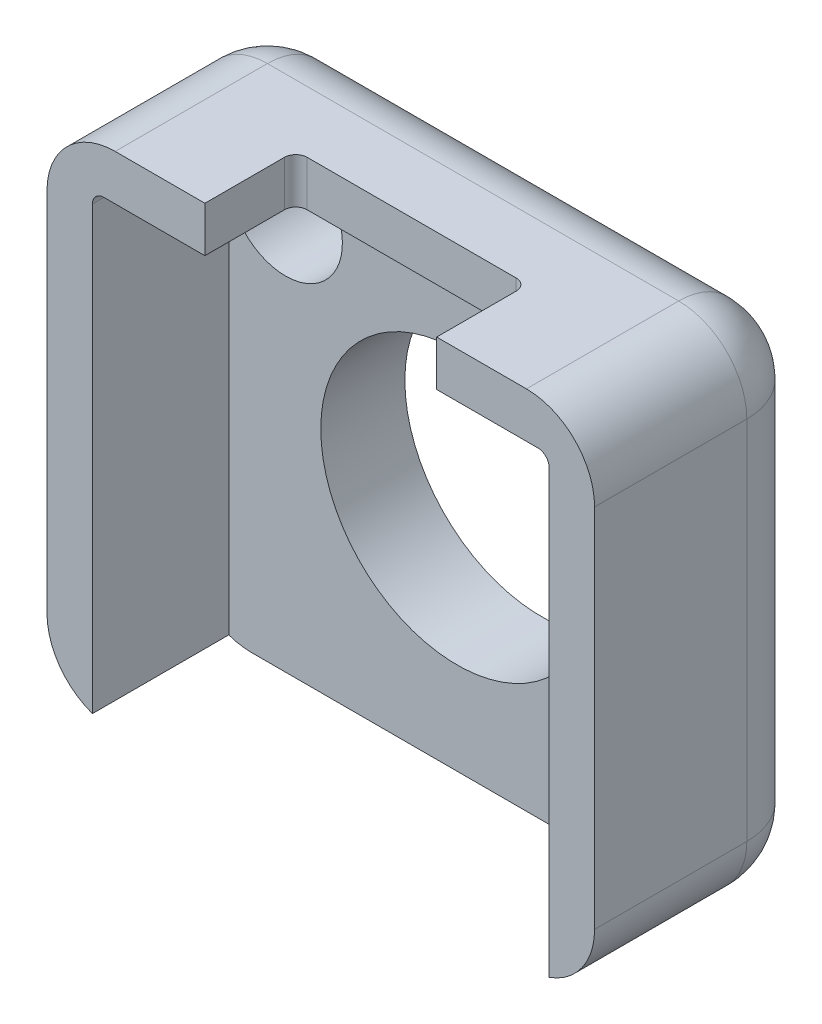
SolidWorks part; units mm, degrees
ref_plane "Front Plane" through (0, 0, 0) normal (0, 0, 1) x (1, 0, 0)
ref_plane "Top Plane" through (0, 0, 0) normal (0, 1, 0) x (1, 0, 0)
ref_plane "Right Plane" through (0, 0, 0) normal (1, 0, 0) x (0, 0, -1)
sketch "Sketch1" plane through (0, 0, 0) normal (0, 0, 1) x (1, 0, 0)
  line L0 (-1.5738, 33.565) -> (-1.5738, 11.465)
  line L1 (-23.6738, 31.565) -> (-3.5738, 31.565)
  line L2 (-23.6738, 31.565) -> (-23.6738, 11.465)
  line L3 (-23.6738, 11.465) -> (-3.5738, 11.465)
  line L4 (-3.5738, 31.565) -> (-3.5738, 11.465)
  line L5 (-25.6738, 33.565) -> (-1.5738, 33.565)
  line L6 (-25.6738, 33.565) -> (-25.6738, 11.465)
  line L7 (-25.6738, 11.465) -> (-23.6738, 11.465)
  line L8 (-3.5738, 11.465) -> (-1.5738, 11.465)
  dimension "D1" = 20.1
  dimension "D2" = 2
extrude "Boss-Extrude2" add sketch "Sketch1" along normal blind 3.7 contours L4 L1 L2 L3 region at (-13.6238, 21.515, 0)
extrude "Boss-Extrude3" add sketch "Sketch1<3>" along normal blind 9.7 contours L4 L8 L0 L5 L6 L7 L2 L1 region at (-1.9008, 22.515, 0)
sketch "Sketch1<3>" plane through (0, 0, 0) normal (0, 0, 1) x (1, 0, 0) same geometry as "Sketch1"
fillet "Fillet1" radius 3 4 edges at (-13.6238, 33.565, 0) (-25.6738, 22.515, 0) (-13.6238, 11.465, 0) (-1.5738, 22.515, 0)
sketch "Sketch2" plane through (0, 0, 9.7) normal (0, 0, 1) x (1, 0, 0)
  line L0 (-18.7238, 33.565) -> (-8.5238, 33.565)
  line L1 (-25.6738, 33.565) -> (-1.5738, 33.565) construction
  line L2 (-8.5238, 33.565) -> (-8.5238, 31.565)
  line L3 (-23.6738, 31.565) -> (-3.5738, 31.565) construction
  line L4 (-8.5238, 31.565) -> (-18.7238, 31.565)
  line L5 (-23.6738, 31.565) -> (-3.5738, 31.565) construction
  line L6 (-18.7238, 31.565) -> (-18.7238, 33.565)
  point P5 (-13.6238, 33.565)
extrude "Cut-Extrude1" cut sketch "Sketch2" against normal blind 4
fillet "Fillet3" radius 3 8 edges at (-24.7951, 12.3437, 0.8787) (-2.4525, 12.3437, 0.8787) (-2.4525, 32.6864, 0.8787) (-24.7951, 32.6864, 0.8787) (-25.6738, 11.465, 6.35) (-1.5738, 11.465, 6.35) (-1.5738, 33.565, 6.35) (-25.6738, 33.565, 6.35)
fillet "Fillet2" radius 0.5 4 edges at (-3.5738, 31.565, 6.7) (-8.5238, 32.565, 5.7) (-18.7238, 32.565, 5.7) (-23.6738, 31.565, 6.7)
sketch "Sketch4" plane through (0, 0, 3.7) normal (0, 0, 1) x (1, 0, 0)
  line L1 (-23.1738, 31.565) -> (-4.0738, 31.565) construction
  line L2 (-23.6738, 31.065) -> (-23.6738, 11.6366) construction
  line L3 (-13.6238, 31.565) -> (-13.6238, 11.465) construction
  line L4 (-22.6738, 11.465) -> (-4.5738, 11.465) construction
  circle A0 centre (-21.1738, 29.065) radius 2.5
  circle A1 centre (-6.0738, 29.065) radius 2.5
  circle A2 centre (-13.6238, 21.515) radius 6
  dimension "D1" = 12
extrude "Cut-Extrude2" cut sketch "Sketch4" against normal through all both and the other way through all
